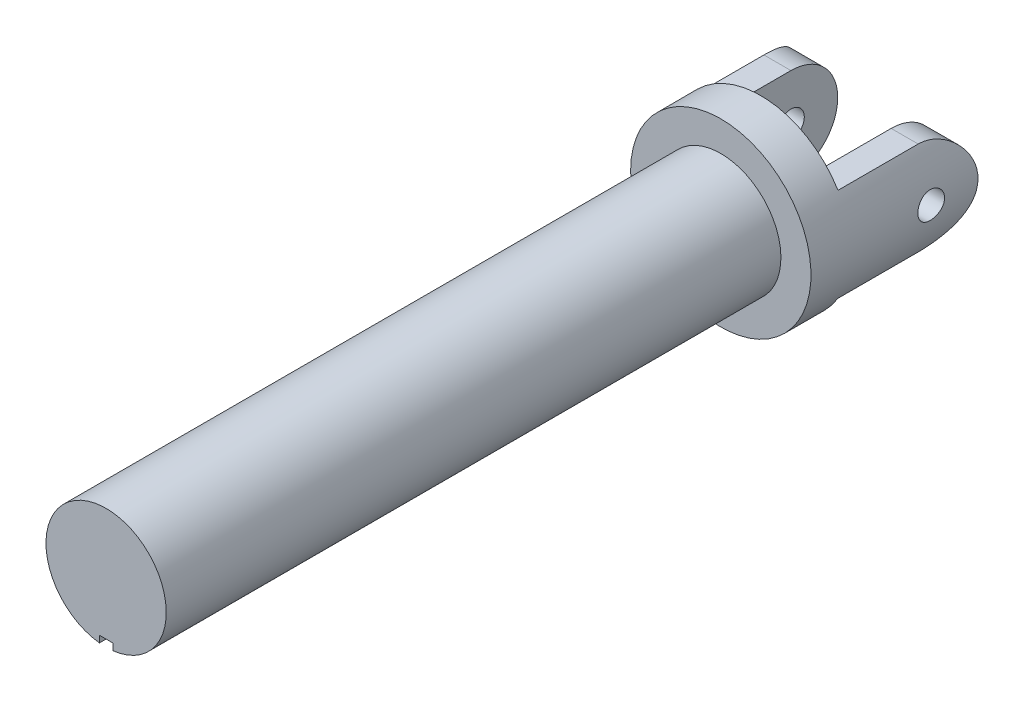
SolidWorks part; units mm, degrees
ref_plane "Front Plane" through (0, 0, 0) normal (0, 0, 1) x (1, 0, 0)
ref_plane "Top Plane" through (0, 0, 0) normal (0, 1, 0) x (1, 0, 0)
ref_plane "Right Plane" through (0, 0, 0) normal (1, 0, 0) x (0, 0, -1)
sketch "Sketch1" plane through (0, 0, 0) normal (0, 0, 1) x (1, 0, 0)
  circle A0 centre (0, 0) radius 4.5
  dimension "D1" = 9
extrude "Yoke" add sketch "Sketch1" along normal mid plane 46 contours A0
sketch "Sketch2" plane through (0, 0, -23) normal (0, 0, -1) x (-1, 0, 0)
  circle A0 centre (0, 0) radius 6.75
  dimension "D1" = 13.5
extrude "U Joint Base" add sketch "Sketch2" along normal blind 3
sketch "Sketch3" plane through (0, 0, -26) normal (0, 0, -1) x (-1, 0, 0)
  line L0 (-5.7717, 3.5) -> (-3.75, 3.5)
  line L1 (-3.75, 3.5) -> (-3.75, -3.5)
  line L2 (-3.75, -3.5) -> (-5.7717, -3.5)
  line L3 (3.75, -3.5) -> (3.75, 3.5)
  line L4 (3.75, 3.5) -> (5.7717, 3.5)
  line L5 (5.7717, -3.5) -> (3.75, -3.5)
  circle A0 centre (0, 0) radius 6.75 construction
  arc A1 (-5.7717, -3.5) -> (-5.7717, 3.5) centre (0, 0) cw
  arc A2 (5.7717, 3.5) -> (5.7717, -3.5) centre (0, 0) cw
  point P16 (0, 0)
  dimension "D2" = 7.5
  dimension "D3" = 7
  dimension "D1" = 2
extrude "U Joint Standups" add sketch "Sketch3" along normal blind 9.5
sketch "Sketch4" plane through (0, 0, 0) normal (1, 0, 0) x (0, 0, -1)
  line L0 (35.5, 3.5) -> (26, 3.5) construction
  line L1 (35.5, -3.5) -> (35.5, 3.5) construction
  line L2 (32, -3.5) -> (35.5, -3.5)
  line L3 (35.5, -3.5) -> (35.5, 0)
  line L4 (35.5, 0) -> (35.5, 3.5)
  line L5 (35.5, 3.5) -> (32, 3.5)
  line L6 (35.5, -3.5) -> (26, -3.5) construction
  arc A0 (35.5, 0) -> (32, 3.5) centre (32, 0) ccw
  arc A1 (32, -3.5) -> (35.5, 0) centre (32, 0) ccw
extrude "Standup Round" cut sketch "Sketch4" against normal through all both and the other way through all contours A1 L2 L3 | A0 L5 L4 region at (0, -2.7182, -34.7182)
sketch "Sketch5" plane through (0, 0, 0) normal (1, 0, 0) x (0, 0, -1)
  circle A0 centre (32, 0) radius 1
  dimension "D1" = 2
extrude "Ball Holes" cut sketch "Sketch5" against normal through all both and the other way through all
sketch "Sketch6" plane through (0, 0, 23) normal (0, 0, 1) x (1, 0, 0)
  line L0 (0.5, -4.4721) -> (0.5, -4.702)
  line L1 (-0.5, -4.4721) -> (-0.5, -3.9721)
  line L2 (-0.5, -3.9721) -> (0.5, -3.9721)
  line L3 (0.5, -3.9721) -> (0.5, -4.4721)
  line L4 (0.5, -4.702) -> (-0.5, -4.702)
  line L5 (-0.5, -4.702) -> (-0.5, -4.4721)
  circle A1 centre (0, 0) radius 4.5 construction
  circle A4 centre (0, 0) radius 4.5 construction
  dimension "D1" = 0.5
  dimension "D2" = 1
  dimension "D3" = 0.5
extrude "Keyway" cut sketch "Sketch6" against normal blind 46 contours L4 L5 L1 L2 L3 L0
